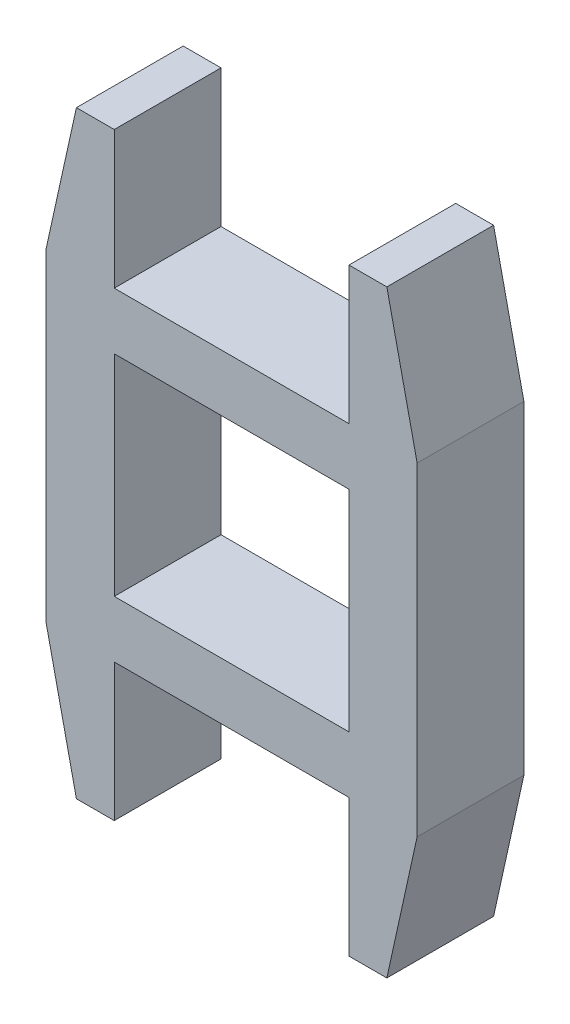
SolidWorks part; units mm, degrees
material "Acrylic (Medium-high impact)"
ref_plane "Front Plane" through (0, 0, 0) normal (0, 0, 1) x (1, 0, 0)
ref_plane "Top Plane" through (0, 0, 0) normal (0, 1, 0) x (1, 0, 0)
ref_plane "Right Plane" through (0, 0, 0) normal (1, 0, 0) x (0, 0, -1)
sketch "Sketch1" plane through (0, 0, 0) normal (0, 0, 1) x (1, 0, 0)
  line L0 (1247.2096, 961.4272) -> (1247.2096, 950.3272)
  line L1 (1263.2096, 948.8272) -> (1243.6096, 948.8272) construction
  line L2 (1247.2096, 947.3272) -> (1243.6096, 947.3272) construction
  line L3 (1247.2096, 961.4272) -> (1259.6096, 961.4272)
  line L4 (1245.2096, 971.6864) -> (1247.2096, 971.6864)
  line L5 (1247.2096, 971.6864) -> (1247.2096, 964.4272)
  line L6 (1247.2096, 955.8772) -> (1259.6096, 955.8772) construction
  line L7 (1259.6096, 964.4272) -> (1247.2096, 964.4272)
  line L8 (1243.6096, 964.4272) -> (1243.6096, 947.3272)
  line L9 (1243.6096, 947.3272) -> (1245.2096, 940.068)
  line L10 (1247.2096, 964.4272) -> (1243.6096, 964.4272) construction
  line L11 (1259.6096, 947.3272) -> (1247.2096, 947.3272)
  line L12 (1243.6096, 964.4272) -> (1245.2096, 971.6864)
  line L13 (1247.2096, 940.068) -> (1247.2096, 947.3272)
  line L14 (1245.2096, 940.068) -> (1247.2096, 940.068)
  line L15 (1247.2096, 950.3272) -> (1259.6096, 950.3272)
  line L16 (1259.6096, 964.4272) -> (1263.2096, 964.4272) construction
  line L17 (1259.6096, 947.3272) -> (1263.2096, 947.3272) construction
  line L18 (1261.6096, 940.068) -> (1259.6096, 940.068)
  line L19 (1253.4096, -38.8351) -> (1253.4096, 49961.1649) construction
  line L20 (1259.6096, 940.068) -> (1259.6096, 947.3272)
  line L21 (1263.2096, 964.4272) -> (1261.6096, 971.6864)
  line L22 (1263.2096, 947.3272) -> (1261.6096, 940.068)
  line L23 (1263.2096, 964.4272) -> (1263.2096, 947.3272)
  line L24 (1259.6096, 971.6864) -> (1259.6096, 964.4272)
  line L25 (1261.6096, 971.6864) -> (1259.6096, 971.6864)
  line L26 (1263.2096, 962.9272) -> (1243.6096, 962.9272) construction
  line L27 (1259.6096, 961.4272) -> (1259.6096, 950.3272)
  point P2 (1263.2096, 955.8772)
  point P14 (1243.6096, 955.8772)
  point P15 (1253.4096, 964.4272)
  point P20 (1253.4096, 962.9272)
  point P26 (1253.4096, 955.8772)
  point P28 (1253.4096, 964.4272)
  point P30 (1253.4096, 961.4272)
  point P31 (1253.4096, 948.8272)
  point P33 (1253.4096, 950.3272)
  point P36 (1253.4096, 947.3272)
  point P38 (1253.4096, 961.4272)
  dimension "D1" = 6.2
  dimension "D2" = 7.2592
  dimension "D3" = 2
  dimension "D4" = 3
  dimension "D5" = 8.55
  dimension "D8" = 3.6
extrude "Boss-Extrude1" add sketch "Sketch1" along normal blind 5.64
